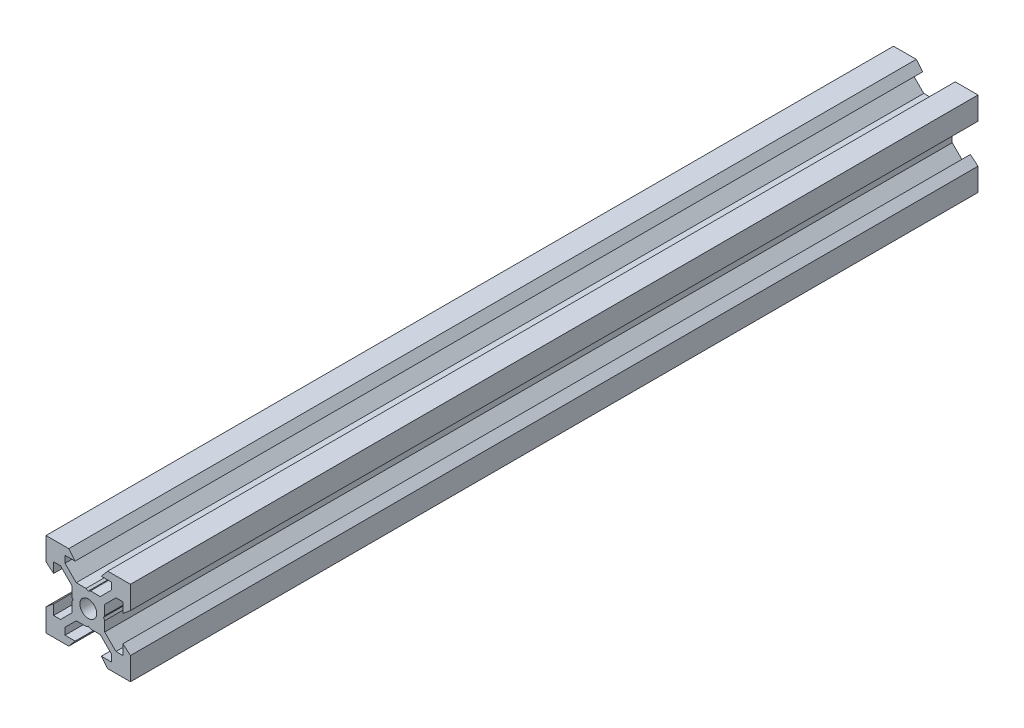
SolidWorks part; units mm, degrees
ref_plane "Front Plane" through (0, 0, 0) normal (0, 0, 1) x (1, 0, 0)
ref_plane "Top Plane" through (0, 0, 0) normal (0, 1, 0) x (1, 0, 0)
ref_plane "Right Plane" through (0, 0, 0) normal (1, 0, 0) x (0, 0, -1)
sketch "Sketch1" plane through (0, 0, 0) normal (0, 0, 1) x (1, 0, 0)
  line L0 (10, 10) -> (4.6104, 10) construction
  line L1 (10, 10) -> (10, 4.6104) construction
  line L2 (10, -10) -> (10, -4.6104) construction
  line L3 (10, -10) -> (4.6104, -10) construction
  line L4 (10, 10) -> (10, 4.6104)
  line L5 (6.5607, 5.5) -> (8.2, 5.5)
  line L6 (5.5, 8.2) -> (5.5, 6.5607)
  line L7 (10, 10) -> (4.6104, 10)
  line L8 (10, 10) -> (10, 4.6104)
  line L9 (6.5607, 5.5) -> (3.9, 2.8393)
  line L10 (5.5, 6.5607) -> (2.8393, 3.9)
  line L11 (10, 4.6104) -> (8.2, 3.1)
  line L12 (4.6104, 10) -> (3.1, 8.2)
  line L13 (8.2, 3.1) -> (8.2, 5.5)
  line L14 (3.1, 8.2) -> (5.5, 8.2)
  line L15 (-6.5607, 5.5) -> (-8.2, 5.5)
  line L16 (6.5607, -5.5) -> (8.2, -5.5)
  line L17 (3.1, -8.2) -> (5.5, -8.2)
  line L18 (8.2, -3.1) -> (8.2, -5.5)
  line L19 (4.6104, -10) -> (3.1, -8.2)
  line L20 (10, -4.6104) -> (8.2, -3.1)
  line L21 (0.5196, -3.9) -> (0, -3.6)
  line L22 (0.5196, 3.9) -> (0, 3.6)
  line L23 (3.6, 0) -> (3.9, -0.5196)
  line L24 (3.9, 0.5196) -> (3.6, 0)
  line L25 (3.9, 0.5196) -> (3.9, 2.8393)
  line L26 (2.8393, 3.9) -> (0.5196, 3.9)
  line L27 (3.9, -2.8393) -> (3.9, -0.5196)
  line L28 (2.8393, -3.9) -> (0.5196, -3.9)
  line L29 (5.5, -6.5607) -> (2.8393, -3.9)
  line L30 (6.5607, -5.5) -> (3.9, -2.8393)
  line L31 (10, -10) -> (10, -4.6104)
  line L32 (10, -10) -> (4.6104, -10)
  line L33 (5.5, -8.2) -> (5.5, -6.5607)
  line L34 (-6.5607, -5.5) -> (-8.2, -5.5)
  line L35 (10, -10) -> (10, -4.6104)
  line L36 (0, 0) -> (0, 8.2) construction
  line L37 (-10, -10) -> (-4.6104, -10) construction
  line L38 (-10, -10) -> (-10, -4.6104) construction
  line L39 (-10, 10) -> (-10, 4.6104) construction
  line L40 (-10, 10) -> (-4.6104, 10) construction
  line L41 (-10, -10) -> (-10, -4.6104)
  line L43 (-5.5, -8.2) -> (-5.5, -6.5607)
  line L44 (-10, -10) -> (-4.6104, -10)
  line L45 (-10, -10) -> (-10, -4.6104)
  line L46 (-6.5607, -5.5) -> (-3.9, -2.8393)
  line L47 (-5.5, -6.5607) -> (-2.8393, -3.9)
  line L48 (-2.8393, -3.9) -> (-0.5196, -3.9)
  line L49 (-3.9, -2.8393) -> (-3.9, -0.5196)
  line L50 (-2.8393, 3.9) -> (-0.5196, 3.9)
  line L51 (-3.9, 0.5196) -> (-3.9, 2.8393)
  line L52 (-3.9, 0.5196) -> (-3.6, 0)
  line L53 (-3.6, 0) -> (-3.9, -0.5196)
  line L54 (-0.5196, 3.9) -> (0, 3.6)
  line L55 (-0.5196, -3.9) -> (0, -3.6)
  line L56 (-10, -4.6104) -> (-8.2, -3.1)
  line L57 (-4.6104, -10) -> (-3.1, -8.2)
  line L58 (-8.2, -3.1) -> (-8.2, -5.5)
  line L59 (-3.1, -8.2) -> (-5.5, -8.2)
  line L60 (-10, -10) -> (10, -10) construction
  line L61 (-10, -10) -> (-10, 10) construction
  line L62 (-3.1, 8.2) -> (-5.5, 8.2)
  line L63 (-8.2, 3.1) -> (-8.2, 5.5)
  line L64 (-4.6104, 10) -> (-3.1, 8.2)
  line L65 (-10, 4.6104) -> (-8.2, 3.1)
  line L66 (-5.5, 6.5607) -> (-2.8393, 3.9)
  line L67 (-6.5607, 5.5) -> (-3.9, 2.8393)
  line L68 (-10, 10) -> (-10, 4.6104)
  line L69 (-10, 10) -> (-4.6104, 10)
  line L70 (-5.5, 8.2) -> (-5.5, 6.5607)
  line L71 (-10, 10) -> (10, 10) construction
  line L72 (-10, 10) -> (-10, 4.6104)
  line L73 (10, -10) -> (10, 10) construction
  line L74 (-10, -10) -> (10, 10) construction
  line L75 (-10, 10) -> (10, -10) construction
  circle A0 centre (0, 0) radius 2
  dimension "D7" = 4
  dimension "D1" = 20
  dimension "D2" = 5.3896
  dimension "D3" = 4.5
  dimension "D4" = 50
  dimension "D5" = 1.8
  dimension "D6" = 1.5104
  dimension "D8" = 5.5
  dimension "D9" = 120
  dimension "D10" = 0.3
  dimension "D11" = 2.3197
  dimension "D12" = 7.8
  dimension "D13" = 7.8
  dimension "D14" = 1.5
  dimension "D15" = 2.6607
extrude "Boss-Extrude1" add sketch "Sketch1" along normal mid plane 200.67 contours L70 L62 L64 L69 L68 L65 L63 L15 L67 L51 L52 L53 L49 L46 L34 L58 L56 L41 L44 L57 L59 L43 L47 L48 L55 L21 L28 L29 L33 L17 L19 L32 L31 L20 L18 L16 L30 L27 L23 L24 L25 L9 L5 L13 L11 L4 L7 L12 L14 L6 L10 region at (9.7172, 7.3052, 0)
